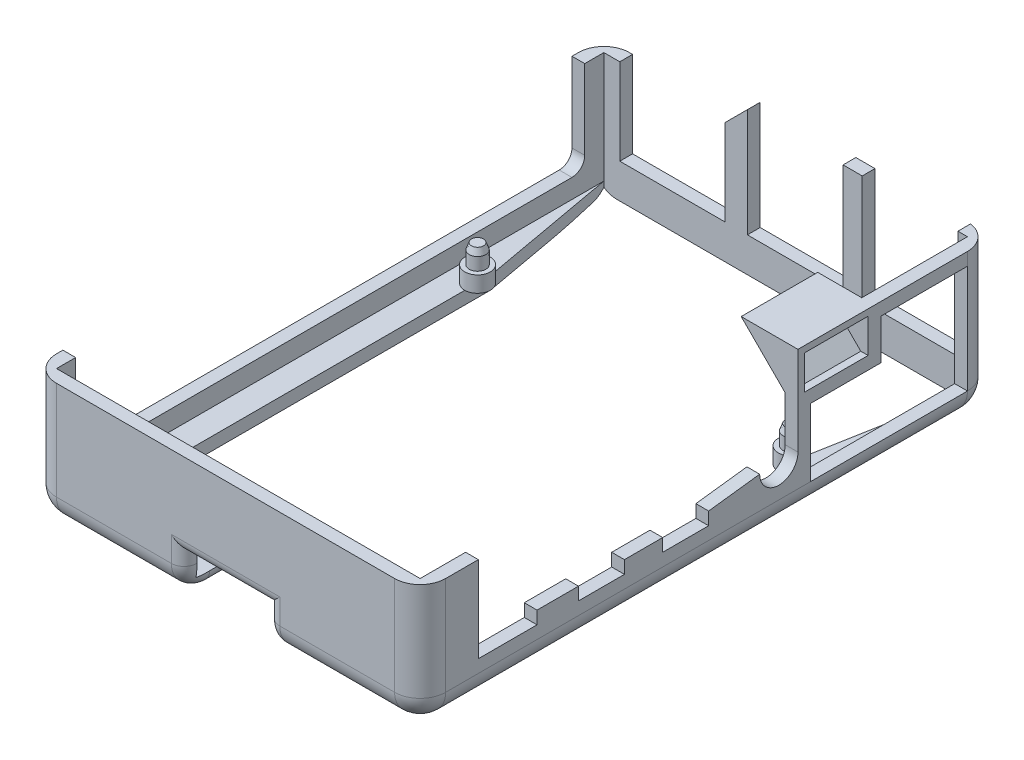
SolidWorks part; units mm, degrees
ref_plane "Płaszczyzna przednia" through (0, 0, 0) normal (0, 0, 1) x (1, 0, 0)
ref_plane "Płaszczyzna górna" through (0, 0, 0) normal (0, 1, 0) x (1, 0, 0)
ref_plane "Płaszczyzna prawa" through (0, 0, 0) normal (1, 0, 0) x (0, 0, -1)
sketch "Szkic1" plane through (0, 0, 0) normal (0, 1, 0) x (1, 0, 0)
  line L0 (-28.5, 42.9) -> (-30.5, 42.9) construction
  line L1 (-28.1, -42.5) -> (28.1, -42.5)
  line L2 (-28.1, -42.5) -> (-28.1, 42.5)
  line L3 (-28.1, 42.5) -> (28.1, 42.5)
  line L4 (28.1, -42.5) -> (28.1, 42.5)
  line L5 (-28.1, -42.5) -> (28.1, 42.5) construction
  line L6 (-28.1, 42.5) -> (28.1, -42.5) construction
  line L7 (28.5, -42.9) -> (-28.5, -42.9)
  line L8 (28.5, -42.9) -> (28.5, 42.9)
  line L9 (28.5, 42.9) -> (-28.5, 42.9)
  line L10 (-28.5, -42.9) -> (-28.5, 42.9)
  line L11 (28.5, -42.9) -> (-28.5, 42.9) construction
  line L12 (28.5, 42.9) -> (-28.5, -42.9) construction
  line L13 (30.5, -44.9) -> (-30.5, -44.9)
  line L14 (30.5, -44.9) -> (30.5, 44.9)
  line L15 (30.5, 44.9) -> (-30.5, 44.9)
  line L16 (-30.5, -44.9) -> (-30.5, 44.9)
  line L17 (30.5, -44.9) -> (-30.5, 44.9) construction
  line L18 (30.5, 44.9) -> (-30.5, -44.9) construction
  line L19 (-28.5, 42.9) -> (-28.5, 44.9) construction
  line L20 (-28.1, 42.5) -> (-28.1, 42.9) construction
  line L21 (-28.1, 42.5) -> (-28.5, 42.5) construction
  point P0 (0, 0)
  point P6 (0, 0)
  point P12 (0, 0)
  dimension "D1" = 56.2
  dimension "D2" = 85
  dimension "D3" = 2
  dimension "D4" = 0.4
extrude "Dodanie-wyciągnięcie2" add sketch "Szkic1" along normal blind 2 contours L1 L4 L3 L2 region at (0, 0, 0)
sketch "Szkic2" plane through (0, 2, 0) normal (0, 1, 0) x (1, 0, 0)
  line L0 (-24.575, -40.975) -> (-24.575, -42.5) construction
  line L1 (-28.1, -42.5) -> (28.1, -42.5) construction
  line L2 (-26.575, -38.975) -> (-28.1, -38.975) construction
  line L3 (-28.1, -42.5) -> (-28.1, 42.5) construction
  line L4 (24.575, -40.975) -> (24.575, -42.5) construction
  line L5 (26.575, -38.975) -> (28.1, -38.975) construction
  line L6 (28.1, -42.5) -> (28.1, 42.5) construction
  line L7 (-26.575, 19.175) -> (-28.1, 19.175) construction
  line L8 (26.575, 19.175) -> (28.1, 19.175) construction
  line L9 (-24.575, 19.175) -> (24.575, 19.175) construction
  line L10 (24.575, 19.175) -> (24.575, -38.975) construction
  circle A0 centre (-24.575, -38.975) radius 2
  circle A1 centre (24.575, -38.975) radius 2
  circle A2 centre (-24.575, 19.175) radius 2
  circle A3 centre (24.575, 19.175) radius 2
  dimension "D2" = 4
  dimension "D3" = 3.525
  dimension "D1" = 58.15
extrude "Dodanie-wyciągnięcie5" add sketch "Szkic2" along normal blind 2.5 contours A2 | A3 | A1 | A0
sketch "Szkic4" plane through (0, 4.5, 0) normal (0, 1, 0) x (1, 0, 0)
  line L0 (0, -38.975) -> (0, 19.175) construction
  line L1 (-24.575, -38.975) -> (24.575, -38.975) construction
  line L2 (-24.575, -38.975) -> (-24.575, 19.175) construction
  line L3 (-24.575, 19.175) -> (24.575, 19.175) construction
  line L4 (24.575, -38.975) -> (24.575, 19.175) construction
  line L5 (24.575, -9.9) -> (-24.575, -9.9) construction
  circle A0 centre (-24.575, 19.175) radius 1.3
  point P8 (0, -8.6)
  point P15 (0, -9.9)
  dimension "D1" = 2.6
extrude "Dodanie-wyciągnięcie6" add sketch "Szkic4" along normal blind 2 contours A0 | A0 region at (-24.575, 4.5, -19.175)
sketch "Szkic6" plane through (0, 6.5, 0) normal (0, 1, 0) x (1, 0, 0)
  circle A0 centre (-24.575, 19.175) radius 1.3
  circle A1 centre (-24.575, 19.175) radius 1.3 construction
  circle M3 centre (-24.575, 19.175) radius 1.3
extrude "Dodanie-wyciągnięcie7" add sketch "Szkic6" along normal blind 1 draft 20 contours M3 | A0 region at (-24.575, 6.5, -19.175)
extrude "Dodanie-wyciągnięcie3" add sketch "Szkic1<4>" along normal up to surface (2 mm away) contours L10 L7 L8 L9 L4 L1 L2 L3 region at (0, 0, 42.797) up to face at (-24.575, 2, 40.975)
sketch "Szkic1<4>" plane through (0, 0, 0) normal (0, 1, 0) x (1, 0, 0) same geometry as "Szkic1"
extrude "Dodanie-wyciągnięcie4" add sketch "Szkic1<5>" along normal up to surface (4.5 mm away) contours L16 L13 L14 L15 L7 L10 L9 L8 region at (0, 0, 43.8144) up to face at (-24.575, 4.5, 40.975)
sketch "Szkic1<5>" plane through (0, 0, 0) normal (0, 1, 0) x (1, 0, 0) same geometry as "Szkic1"
mirror "Lustro1" about plane through (0, 0, 0) normal (1, 0, 0) of "Dodanie-wyciągnięcie7", "Dodanie-wyciągnięcie6"
ref_plane "Płaszczyzna miedzy kolkami" through (0, 0, 9.9) normal (0, 0, 1) x (1, 0, 0)
mirror "Lustro2" about plane through (0, 0, 9.9) normal (0, 0, 1) of "Dodanie-wyciągnięcie7", "Lustro1", "Dodanie-wyciągnięcie6"
sketch "Szkic12" plane through (0, 0, 44.9) normal (0, 0, 1) x (1, 0, 0)
  line L0 (30.5, 0) -> (-30.5, 0) construction
  line L1 (-6.5, 0) -> (6.5, 0)
  line L2 (-6.5, 0) -> (-6.5, 4.5)
  line L3 (-6.5, 4.5) -> (6.5, 4.5)
  line L4 (6.5, 0) -> (6.5, 4.5)
  line L5 (30.5, 4.5) -> (-30.5, 4.5) construction
  line L6 (-6.5, 2.25) -> (-30.5, 2.25) construction
  line L7 (-30.5, 4.5) -> (-30.5, 0) construction
  line L8 (6.5, 2.25) -> (30.5, 2.25) construction
  line L9 (30.5, 4.5) -> (30.5, 0) construction
  dimension "D1" = 13
extrude "Wytnij-wyciągnięcie4" cut sketch "Szkic12" against normal blind 10
sketch "Szkic13" plane through (0, 4.5, 0) normal (0, 1, 0) x (1, 0, 0)
  line L12 (-6.5, -44.9) -> (-6.5, -42.9)
  line L13 (-6.5, -42.9) -> (-28.5, -42.9)
  line L14 (-28.5, -42.9) -> (-28.5, 42.9)
  line L15 (-28.5, 42.9) -> (28.5, 42.9)
  line L16 (28.5, 42.9) -> (28.5, -42.9)
  line L17 (28.5, -42.9) -> (6.5, -42.9)
  line L18 (6.5, -42.9) -> (6.5, -44.9)
  line L19 (6.5, -44.9) -> (30.5, -44.9)
  line L20 (30.5, -44.9) -> (30.5, 44.9)
  line L21 (30.5, 44.9) -> (-30.5, 44.9)
  line L22 (-30.5, 44.9) -> (-30.5, -44.9)
  line L23 (-30.5, -44.9) -> (-6.5, -44.9)
  line L24 (-6.5, -44.9) -> (-6.5, -42.9)
  line L25 (-6.5, -42.9) -> (-28.5, -42.9)
  line L26 (-28.5, -42.9) -> (-28.5, 42.9)
  line L27 (-28.5, 42.9) -> (28.5, 42.9)
  line L28 (28.5, 42.9) -> (28.5, -42.9)
  line L29 (28.5, -42.9) -> (6.5, -42.9)
  line L30 (6.5, -42.9) -> (6.5, -44.9)
  line L31 (6.5, -44.9) -> (30.5, -44.9)
  line L32 (30.5, -44.9) -> (30.5, 44.9)
  line L33 (30.5, 44.9) -> (-30.5, 44.9)
  line L34 (-30.5, 44.9) -> (-30.5, -44.9)
  line L35 (-30.5, -44.9) -> (-6.5, -44.9)
  dimension "D1" = 0
extrude "Dodanie-wyciągnięcie8" add sketch "Szkic13" along normal blind 1.45 contours L24 L25 L26 L27 L28 L29 L30 L31 L32 L33 L34 L35
sketch "Szkic14" plane through (0, 5.95, 0) normal (0, 1, 0) x (1, 0, 0)
  line L1 (-30.5, -44.9) -> (30.5, -44.9)
  line L2 (-30.5, -44.9) -> (-30.5, 44.9)
  line L3 (-30.5, 44.9) -> (30.5, 44.9)
  line L4 (30.5, -44.9) -> (30.5, 44.9)
  line L5 (-28.5, -42.9) -> (28.5, -42.9)
  line L6 (-28.5, -42.9) -> (-28.5, 42.9)
  line L7 (-28.5, 42.9) -> (28.5, 42.9)
  line L8 (28.5, -42.9) -> (28.5, 42.9)
extrude "Dodanie-wyciągnięcie9" add sketch "Szkic14" along normal blind 17
sketch "Szkic15" plane through (0, 0, -44.9) normal (0, 0, -1) x (-1, 0, 0)
  line L0 (-30.5, 22.95) -> (30.5, 22.95) construction
  line L1 (-27, 22.95) -> (26, 22.95)
  line L2 (-27, 22.95) -> (-27, 5.95)
  line L3 (-27, 5.95) -> (26, 5.95)
  line L4 (26, 22.95) -> (26, 5.95)
  line L5 (-27, 5.95) -> (-30.5, 5.95) construction
  line L6 (-30.5, 22.95) -> (-30.5, 0) construction
  line L7 (9.5, 5.95) -> (9.5, 22.95)
  line L8 (30.5, 22.95) -> (30.5, 0) construction
  line L9 (-30.5, 4.5) -> (30.5, 4.5) construction
  line L10 (-22.575, 4.5) -> (-26.575, 4.5) construction
  line L11 (6, 5.95) -> (6, 22.95)
  line L12 (-12, 5.95) -> (-12, 22.95)
  line L13 (-9, 5.95) -> (-9, 22.95)
  line L14 (-27, 14.45) -> (-12, 14.45) construction
  line L15 (-9, 14.45) -> (6, 14.45) construction
  line M9 (30.5, 22.95) -> (-30.5, 22.95)
  dimension "D1" = 3.5
  dimension "D2" = 1.45
  dimension "D3" = 4.5
  dimension "D4" = 16.5
  dimension "D5" = 15
  dimension "D6" = 3
extrude "Wytnij-wyciągnięcie5" cut sketch "Szkic15" against normal up to surface (2 mm away) contours L7 L3 L4 M9 | L13 L3 L11 M9 | L3 L12 L1 L2 region at (19.5, 14.45, -44.9) region at (1.5, 14.45, -44.9) region at (-17.75, 14.45, -44.9) up to face at (0, 12.475, -42.9)
sketch "Szkic16" plane through (30.5, 0, 0) normal (1, 0, 0) x (0, 0, -1)
  line L0 (-44.9, 22.95) -> (44.9, 22.95) construction
  line L1 (-36.975, 22.95) -> (17.175, 22.95)
  line L2 (-36.975, 22.95) -> (-36.975, 6)
  line L3 (-36.975, 6) -> (17.175, 6)
  line L4 (17.175, 22.95) -> (17.175, 6)
  line L5 (-36.975, 2) -> (-36.975, 4.5) construction
  line L6 (17.175, 4.5) -> (17.175, 2) construction
  line L7 (-36.975, 6) -> (-36.975, 4.5) construction
  line L8 (-36.975, 4.5) -> (17.175, 4.5) construction
  line L9 (17.175, 4.5) -> (17.175, 6) construction
  line L10 (21.175, 4.5) -> (17.175, 4.5) construction
  line L11 (-35.775, 6) -> (-35.775, 22.95)
  line L12 (-26.575, 6) -> (-26.575, 22.95)
  line L13 (-20.075, 6) -> (-20.075, 22.95)
  line L14 (-12.875, 6) -> (-12.875, 22.95)
  line L15 (-6.875, 6) -> (-6.875, 22.95)
  line L16 (0.325, 6) -> (0.325, 22.95)
  line L17 (8.325, 6) -> (8.325, 22.95)
  line L18 (14.325, 6) -> (14.325, 22.95)
  line L19 (17.175, 6) -> (-36.975, 6) construction
  line L20 (17.175, 12) -> (-36.975, 12)
  line L21 (-36.975, 10) -> (17.175, 10)
  line L22 (-36.975, 8) -> (17.175, 8)
  line L23 (-37.975, 8) -> (-37.975, 10) construction
  line L24 (-37.975, 8) -> (-37.975, 6) construction
  line L25 (0.325, 8) -> (8.325, 9)
  circle A0 centre (11.325, 9) radius 3
  point P42 (0.325, 8)
  dimension "D1" = 1.5
  dimension "D2" = 9.2
  dimension "D3" = 7.2
  dimension "D4" = 7.2
  dimension "D5" = 6
  dimension "D6" = 1.2
  dimension "D7" = 6.5
  dimension "D8" = 6
  dimension "D9" = 8
  dimension "D10" = 0
  dimension "D11" = 4
  dimension "D12" = 1
extrude "Wytnij-wyciągnięcie6" cut sketch "Szkic16" against normal up to surface (2 mm away) contours L20 L12 L1 L11 | L11 L21 L12 L20 | L11 L22 L12 L21 | L22 L11 L3 L12 | L20 L14 L1 L13 | L13 L21 L14 L20 | L13 L22 L14 L21 | L22 L13 L3 L14 | L20 L16 L1 L15 | L15 L21 L16 L20 | L15 L22 L16 L21 | L22 L15 L3 L16 | L20 L17 L1 L16 | L16 L21 L17 L20 | L16 L25 L17 L21 | L20 L15 L1 L14 | L14 L21 L15 L20 | L14 L22 L15 L21 | L20 L13 L1 L12 | L12 L21 L13 L20 | L12 L22 L13 L21 | L21 A0 L22 | L21 A0 | L22 A0 | A0 L20 L17 L21 | A0 L21 L18 L20 | L20 L18 L1 L17 | A0 L18 L21 | A0 L21 L17 region at (30.5, 17.475, 31.175) region at (30.5, 17.475, 23.325) region at (30.5, 11, 31.175) region at (30.5, 17.475, 16.475) region at (30.5, 11, 23.325) region at (30.5, 9, 31.175) region at (30.5, 17.475, 9.875) region at (30.5, 11, 16.475) region at (30.5, 9, 23.325) region at (30.5, 7, 31.175) region at (30.5, 17.475, 3.275) region at (30.5, 11, 9.875) region at (30.5, 9, 16.475) region at (30.5, 17.475, -4.325) region at (30.5, 11, 3.275) region at (30.5, 9, 9.875) region at (30.5, 7, 16.475) region at (30.5, 17.475, -11.325) region at (30.5, 11, -4.325) region at (30.5, 9, 3.275) region at (30.5, 11.3775, -9.0138) region at (30.5, 9.2222, -3.8806) region at (30.5, 7, 3.275) region at (30.5, 11.3775, -13.6362) region at (30.5, 9.7515, -8.3762) region at (30.5, 10.8284, -11.325) region at (30.5, 9.7515, -14.2738) region at (30.5, 9, -11.325) region at (30.5, 7.1716, -11.325) up to face at (28.5, 12.475, 0)
sketch "Szkic17" plane through (-30.5, 0, 0) normal (-1, 0, 0) x (0, 0, 1)
  line L0 (-44.9, 22.95) -> (44.9, 22.95) construction
  line L1 (-42.9, 22.95) -> (44.9, 22.95)
  line L2 (-42.9, 22.95) -> (-42.9, 2)
  line L3 (-42.9, 2) -> (44.9, 2)
  line L4 (44.9, 22.95) -> (44.9, 2)
  line L5 (44.9, 22.95) -> (44.9, 0) construction
  line L6 (-42.9, 22.95) -> (-42.9, 2) construction
  line L8 (34.9, 2) -> (42.9, 2) construction
extrude "Wytnij-wyciągnięcie7" [suppressed] cut sketch "Szkic17" against normal up to surface (2 mm away) up to face at (-28.5, 12.475, 0)
fillet "Zaokrąglenie1" radius 4 9 edges at (-18.5, 0, 44.9) (18.5, 0, 44.9) (30.5, 0, 0) (-30.5, 0, 0) (0, 0, -44.9) (-30.5, 11.475, -44.9) (30.5, 11.475, -44.9) (30.5, 11.475, 44.9) (-30.5, 11.475, 44.9)
fillet "Zaokrąglenie2" radius 2 8 edges at (6.5, 4.975, 44.9) (-6.5, 4.975, 44.9) (-6.5, 0, 37.9) (0, 5.95, 44.9) (6.5, 0, 37.9) (6.5, 1.1716, 43.7284) (-6.5, 1.1716, 43.7284) (0, 0, 34.9)
sketch "Szkic18" plane through (0, 0, -14.325) normal (0, 0, 1) x (1, 0, 0)
  line L0 (28.5, 22.95) -> (21.6, 22.95)
  line L1 (21.6, 22.95) -> (28.5, 16.05)
  line L2 (28.5, 9) -> (28.5, 22.95) construction
  line L3 (28.5, 16.05) -> (28.5, 22.95)
  dimension "D1" = 6.9
  dimension "D2" = 45
extrude "Dodanie-wyciągnięcie10" add sketch "Szkic18" against normal blind 12
sketch "Szkic19" plane through (30.5, 0, 0) normal (1, 0, 0) x (0, 0, -1)
  line L0 (14.325, 21.95) -> (15.325, 21.95)
  line L1 (14.325, 9) -> (14.325, 22.95) construction
  line L2 (15.325, 21.95) -> (15.325, 22.95)
  line L3 (14.325, 22.95) -> (40.9, 22.95) construction
  line L5 (15.325, 21.95) -> (25.325, 21.95)
  line L6 (15.325, 21.95) -> (15.325, 16.6161)
  line L7 (15.325, 16.6161) -> (25.325, 16.6161)
  line L8 (25.325, 21.95) -> (25.325, 16.6161)
  dimension "D1" = 1
  dimension "D2" = 10
extrude "Wytnij-wyciągnięcie8" cut sketch "Szkic19" along direction (-1, 0, 0) on the side against the normal up to vertex (8.9 mm away) contours L8 L5 L6 L7 region at (30.5, 19.283, -20.325) up to point (21.6, 22.95, -14.325)
sketch "Szkic20" plane through (0, 0, -25.325) normal (0, 0, 1) x (1, 0, 0)
  line L4 (30.5, 11.95) -> (22.6, 11.95)
  line L6 (24.0142, 21.95) -> (29.3481, 16.6161)
  line L7 (23.3071, 22.6571) -> (28.641, 17.3232) construction
  line L8 (27.9339, 16.6161) -> (30.5, 16.6161)
  line L9 (30.5, 16.6161) -> (30.5, 21.95)
  line L10 (30.5, 21.95) -> (22.6, 21.95)
  line L11 (22.6, 21.95) -> (27.9339, 16.6161)
  line L12 (27.9339, 16.6161) -> (30.5, 16.6161)
  line L13 (30.5, 16.6161) -> (30.5, 21.95)
  line L14 (30.5, 21.95) -> (22.6, 21.95)
  line L15 (22.6, 21.95) -> (27.9339, 16.6161)
  line M6 (27.9339, 16.6161) -> (30.5, 16.6161)
  line M8 (30.5, 21.95) -> (22.6, 21.95)
  line M9 (22.6, 21.95) -> (27.9339, 16.6161)
  dimension "D1" = 0
  dimension "D2" = 10
  dimension "D3" = 1
extrude "Dodanie-wyciągnięcie11" add sketch "Szkic20" along normal up to surface (10 mm away) contours L6 M8 M9 M6 region at (25.9741, 19.283, -25.325) up to face at (27.8835, 19.283, -15.325)
sketch "Szkic21" plane through (0, 0, 0) normal (0, -1, 0) x (-1, 0, 0)
  line L1 (24.575, -36.975) -> (-24.575, -36.975)
  line L6 (-9.5, -32.9) -> (-9.5, -36.975)
  line L7 (9.5, -32.9) -> (9.5, -36.975)
  line L8 (8.5, -31.9) -> (-8.5, -31.9)
  line L9 (-8.5, -40.9) -> (-8.5, -32.9) construction
  line L10 (-24.575, -36.975) -> (-24.575, 21.175)
  line L11 (24.575, -36.975) -> (24.575, 21.175)
  line L13 (-28.5, -42.9) -> (-28.5, 42.9) construction
  line L14 (-28.5, 42.9) -> (28.5, 42.9) construction
  line L15 (28.5, -42.9) -> (28.5, 42.9) construction
  line L16 (-28.5, -42.9) -> (-28.5, 42.9)
  line L17 (-28.5, 42.9) -> (28.5, 42.9)
  line L18 (28.5, -42.9) -> (28.5, 42.9)
  line L19 (-24.575, 21.175) -> (-28.5, 42.9)
  line L20 (24.575, 21.175) -> (28.5, 42.9)
  circle A2 centre (-24.575, -38.975) radius 2 construction
  arc A3 (-8.5, -31.9) -> (-9.5, -32.9) centre (-8.5, -32.9) ccw
  arc A4 (8.5, -31.9) -> (9.5, -32.9) centre (8.5, -32.9) cw
  circle A6 centre (24.575, 19.175) radius 2 construction
  circle A7 centre (24.575, -38.975) radius 2 construction
  circle A9 centre (-24.575, 19.175) radius 2 construction
  line M15 (26.5, 40.9) -> (-26.5, 40.9)
  dimension "D1" = 1
extrude "Wytnij-wyciągnięcie9" cut sketch "Szkic21" against normal up to surface (2 mm away) contours L8 M15 | M15 region at (0, 0, -4.5919) up to face at (-0.0007, 2, 23.6228)
sketch "Szkic22" plane through (0, 0, -44.9) normal (0, 0, -1) x (-1, 0, 0)
  line L0 (6, 22.95) -> (9.5, 19.45)
  line L1 (9.5, 5.95) -> (9.5, 22.95) construction
  line L2 (9.5, 19.45) -> (9.5, 22.95)
  line L3 (6, 22.95) -> (9.5, 22.95) construction
  line L4 (9.5, 22.95) -> (6, 22.95)
  line L5 (9.5, 19.45) -> (25.9689, 19.45) construction
  line L6 (25.9689, 19.45) -> (30.5, 19.45)
  line L7 (30.5, 22.95) -> (30.5, 4) construction
  line L8 (30.5, 19.45) -> (30.5, 22.95)
  line L9 (30.5, 22.95) -> (26, 22.95)
  line L10 (26, 22.95) -> (9.5, 22.95) construction
  line L11 (25.9689, 19.45) -> (26, 22.95)
  dimension "D1" = 3.5
extrude "Wytnij-wyciągnięcie10" cut sketch "Szkic22" against normal up to surface (2 mm away) up to face at (0.65, 11.3202, -42.9)
sketch "Szkic23" plane through (-30.5, 0, 0) normal (-1, 0, 0) x (0, 0, 1)
  line L0 (-42.9, 19.45) -> (44.9, 19.45)
  line L1 (44.9, 22.95) -> (44.9, 4) construction
  line L2 (44.9, 19.45) -> (44.9, 22.95)
  line L3 (44.9, 22.95) -> (-42.9, 22.95)
  line L4 (-42.9, 22.95) -> (-42.9, 19.45)
extrude "Wytnij-wyciągnięcie11" cut sketch "Szkic23" against normal up to surface (2 mm away) up to face at (-28.5, 13.87, -8.58)
sketch "Szkic24" plane through (0, 0, 44.9) normal (0, 0, 1) x (1, 0, 0)
  line L0 (-28.5, 22.95) -> (30.5, 22.95)
  line L1 (-28.5, 22.95) -> (-28.5, 19.45)
  line L2 (-28.5, 19.45) -> (30.5, 19.45)
  line L3 (30.5, 22.95) -> (30.5, 4) construction
  line L4 (30.5, 19.45) -> (30.5, 22.95)
extrude "Wytnij-wyciągnięcie12" cut sketch "Szkic24" against normal up to surface (2 mm away) up to face at (-2.5903, 8.5839, 42.9)
sketch "Szkic25" plane through (30.5, 0, 0) normal (1, 0, 0) x (0, 0, -1)
  line L0 (-42.9, 22.95) -> (-42.9, 19.45)
  line L1 (-42.9, 19.45) -> (-35.775, 19.45)
  line L2 (-35.775, 6) -> (-35.775, 22.95) construction
  line L3 (-35.775, 19.45) -> (-35.775, 22.95)
  line L4 (-40.9, 22.95) -> (-35.775, 22.95) construction
  line L5 (-35.775, 22.95) -> (-42.9, 22.95)
extrude "Wytnij-wyciągnięcie13" cut sketch "Szkic25" against normal up to surface (2 mm away) up to face at (28.5, 10.8341, 7.1352)
sketch "Szkic26" plane through (-30.5, 0, 0) normal (-1, 0, 0) x (0, 0, 1)
  line L0 (-39.9, 19.45) -> (-39.9, 7)
  line L1 (-40.9, 19.45) -> (40.9, 19.45) construction
  line L2 (-37.9, 5) -> (37.9, 5)
  line L3 (39.9, 7) -> (39.9, 19.45)
  line L4 (-40.9, 19.45) -> (-40.9, 4) construction
  line L5 (40.9, 4) -> (40.9, 19.45) construction
  line L6 (-40.9, 4) -> (40.9, 4) construction
  line L7 (-39.9, 19.45) -> (39.9, 19.45)
  arc A0 (-39.9, 7) -> (-37.9, 5) centre (-37.9, 7) ccw
  arc A1 (37.9, 5) -> (39.9, 7) centre (37.9, 7) ccw
  point P16 (0, 0)
  point P17 (37.3797, 7.5203)
  point P18 (-27.8036, 17.0964)
  point P19 (28.0324, 16.8676)
  point P20 (-37.6418, 7.2582)
  dimension "D4" = 2
  dimension "D1" = 1
  dimension "D2" = 1
  dimension "D3" = 1
extrude "Wytnij-wyciągnięcie14" cut sketch "Szkic26" against normal up to surface (2 mm away) contours L3 L7 L0 A0 L2 A1 up to face at (-28.5, 10.725, 0)
sketch "Szkic27" plane through (30.5, 0, 0) normal (1, 0, 0) x (0, 0, -1)
  line L0 (16.325, 14.6161) -> (27.325, 14.6161)
  line L1 (27.325, 14.6161) -> (27.325, 20.95)
  line L2 (27.325, 20.95) -> (40.9, 20.95)
  line L3 (40.9, 4) -> (40.9, 22.95) construction
  line L4 (40.9, 20.95) -> (40.9, 4)
  line L5 (40.9, 4) -> (16.325, 4)
  line L6 (-40.9, 4) -> (40.9, 4) construction
  line L7 (16.325, 4) -> (16.325, 14.6161)
  line L10 (15.325, 16.6161) -> (25.325, 16.6161) construction
  line L11 (25.325, 21.95) -> (25.325, 16.6161) construction
  line L12 (14.325, 9) -> (14.325, 22.95) construction
  line L13 (14.325, 22.95) -> (40.9, 22.95) construction
  dimension "D1" = 2
  dimension "D2" = 2
  dimension "D3" = 2
  dimension "D4" = 2
extrude "Wytnij-wyciągnięcie16" cut sketch "Szkic27" against normal up to surface (2 mm away) up to face at (28.5, 10.0905, 5.4321)
